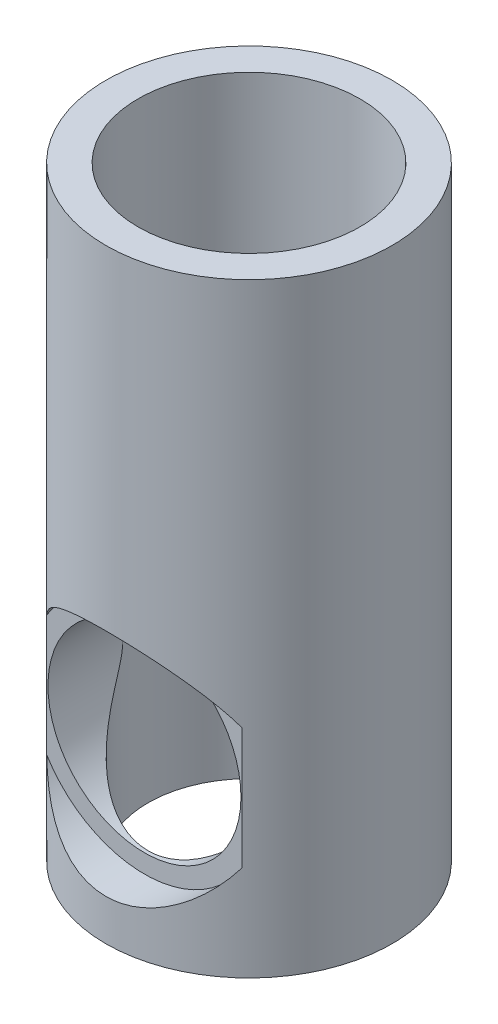
SolidWorks part; units mm, degrees
material "PTFE (general)"
ref_plane "Front Plane" through (0, 0, 0) normal (0, 0, 1) x (1, 0, 0)
ref_plane "Top Plane" through (0, 0, 0) normal (0, 1, 0) x (1, 0, 0)
ref_plane "Right Plane" through (0, 0, 0) normal (1, 0, 0) x (0, 0, -1)
sketch "Sketch1" plane through (0, 0, 0) normal (0, 1, 0) x (1, 0, 0)
  circle A0 centre (0, 0) radius 8.9
  circle A1 centre (0, 0) radius 6.28
  dimension "D1" = 17.8
  dimension "D2" = 12.56
extrude "Boss-Extrude1" add sketch "Sketch1" against normal blind 19.1
sketch "Sketch2" plane through (0, 0, 0) normal (0, -1, 0) x (-1, 0, 0)
  circle A0 centre (0, 0) radius 8.9
  circle A1 centre (0, 0) radius 6.9
  dimension "D1" = 17.8
  dimension "D2" = 13.8
extrude "Boss-Extrude2" add sketch "Sketch2" against normal blind 18.5
sketch "Sketch3" plane through (0, 0, 0) normal (0, 0, 1) x (1, 0, 0)
  line L1 (6.28, 0) -> (-6.28, 0) construction
  circle A0 centre (0, -9.4) radius 7.15
  dimension "D1" = 14.3
  dimension "D2" = 9.4
extrude "Cut-Extrude5" cut sketch "Sketch3" along normal through all from offset 6.5
sketch "Sketch6" plane through (0, 0, 6.5) normal (0, 0, 1) x (1, 0, 0)
  circle A0 centre (0, -9.4) radius 6
  dimension "D1" = 12
extrude "Cut-Extrude6" cut sketch "Sketch6" against normal blind 7 and the other way through all
